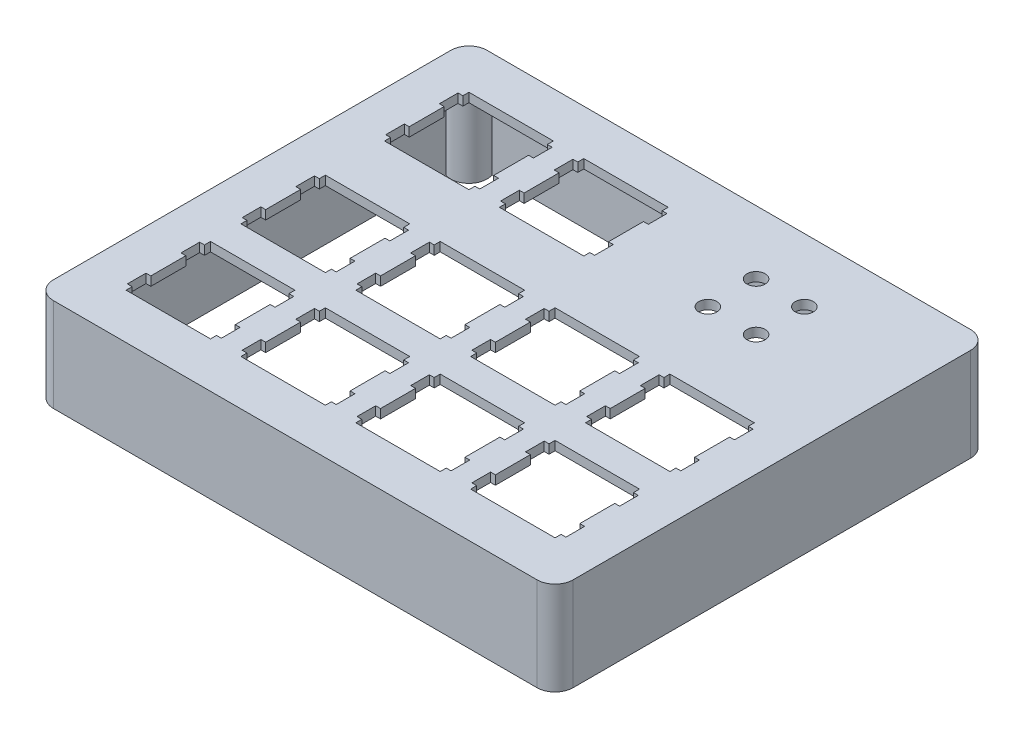
SolidWorks part; units mm, degrees
material "ABS"
ref_plane "Front" through (0, 0, 0) normal (0, 0, 1) x (1, 0, 0)
ref_plane "Top" through (0, 0, 0) normal (0, 1, 0) x (1, 0, 0)
ref_plane "Right" through (0, 0, 0) normal (1, 0, 0) x (0, 0, -1)
sketch "Model" plane through (0, 0, -8.6083) normal (0, 1, 0) x (1, 0, 0)
  line L0 (59.625, 24.9677) -> (64.675, 24.9677) construction
  line L1 (62.15, 24.9677) -> (62.15, 48.7802) construction
  line L3 (58.15, 52.7802) -> (66.15, 52.7802) construction
  line L4 (58.15, 52.7802) -> (58.15, 44.7802) construction
  line L5 (58.15, 44.7802) -> (66.15, 44.7802) construction
  line L6 (66.15, 52.7802) -> (66.15, 44.7802) construction
  line L7 (58.15, 52.7802) -> (66.15, 44.7802) construction
  line L8 (58.15, 44.7802) -> (66.15, 52.7802) construction
  circle A0 centre (58.15, 52.7802) radius 1.5
  circle A1 centre (66.15, 52.7802) radius 1.5
  circle A2 centre (66.15, 44.7802) radius 1.5
  circle A3 centre (58.15, 44.7802) radius 1.5
  point P5 (40.575, 48.7802)
  line B0 (86.201, -8.6083) -> (0, -8.6083)
  line B1 (0, -8.6083) -> (0, 63.3047)
  line B2 (0, 63.3047) -> (86.201, 63.3047)
  line B3 (86.201, 63.3047) -> (86.201, -8.6083)
  line B4 (64.675, 12.9177) -> (64.675, 11.9177)
  line B5 (64.675, 11.9177) -> (63.875, 11.9177)
  line B6 (63.875, 11.9177) -> (63.875, 8.8177)
  line B7 (63.875, 8.8177) -> (64.675, 8.8177)
  line B8 (64.675, 8.8177) -> (64.675, 3.0177)
  line B9 (64.675, 3.0177) -> (63.875, 3.0177)
  line B10 (63.875, 3.0177) -> (63.875, -0.0823)
  line B11 (63.875, -0.0823) -> (64.675, -0.0823)
  line B12 (64.675, -0.0823) -> (64.675, -1.0823)
  line B13 (64.675, -1.0823) -> (78.675, -1.0823)
  line B14 (78.675, -1.0823) -> (78.675, -0.0823)
  line B15 (78.675, -0.0823) -> (79.475, -0.0823)
  line B16 (79.475, -0.0823) -> (79.475, 3.0177)
  line B17 (79.475, 3.0177) -> (78.675, 3.0177)
  line B18 (78.675, 3.0177) -> (78.675, 8.8177)
  line B19 (78.675, 8.8177) -> (79.475, 8.8177)
  line B20 (79.475, 8.8177) -> (79.475, 11.9177)
  line B21 (79.475, 11.9177) -> (78.675, 11.9177)
  line B22 (78.675, 11.9177) -> (78.675, 12.9177)
  line B23 (78.675, 12.9177) -> (64.675, 12.9177)
  line B24 (45.625, 12.9177) -> (45.625, 11.9177)
  line B25 (45.625, 11.9177) -> (44.825, 11.9177)
  line B26 (44.825, 11.9177) -> (44.825, 8.8177)
  line B27 (44.825, 8.8177) -> (45.625, 8.8177)
  line B28 (45.625, 8.8177) -> (45.625, 3.0177)
  line B29 (45.625, 3.0177) -> (44.825, 3.0177)
  line B30 (44.825, 3.0177) -> (44.825, -0.0823)
  line B31 (44.825, -0.0823) -> (45.625, -0.0823)
  line B32 (45.625, -0.0823) -> (45.625, -1.0823)
  line B33 (45.625, -1.0823) -> (59.625, -1.0823)
  line B34 (59.625, -1.0823) -> (59.625, -0.0823)
  line B35 (59.625, -0.0823) -> (60.425, -0.0823)
  line B36 (60.425, -0.0823) -> (60.425, 3.0177)
  line B37 (60.425, 3.0177) -> (59.625, 3.0177)
  line B38 (59.625, 3.0177) -> (59.625, 8.8177)
  line B39 (59.625, 8.8177) -> (60.425, 8.8177)
  line B40 (60.425, 8.8177) -> (60.425, 11.9177)
  line B41 (60.425, 11.9177) -> (59.625, 11.9177)
  line B42 (59.625, 11.9177) -> (59.625, 12.9177)
  line B43 (59.625, 12.9177) -> (45.625, 12.9177)
  line B44 (26.575, 12.9177) -> (26.575, 11.9177)
  line B45 (26.575, 11.9177) -> (25.775, 11.9177)
  line B46 (25.775, 11.9177) -> (25.775, 8.8177)
  line B47 (25.775, 8.8177) -> (26.575, 8.8177)
  line B48 (26.575, 8.8177) -> (26.575, 3.0177)
  line B49 (26.575, 3.0177) -> (25.775, 3.0177)
  line B50 (25.775, 3.0177) -> (25.775, -0.0823)
  line B51 (25.775, -0.0823) -> (26.575, -0.0823)
  line B52 (26.575, -0.0823) -> (26.575, -1.0823)
  line B53 (26.575, -1.0823) -> (40.575, -1.0823)
  line B54 (40.575, -1.0823) -> (40.575, -0.0823)
  line B55 (40.575, -0.0823) -> (41.375, -0.0823)
  line B56 (41.375, -0.0823) -> (41.375, 3.0177)
  line B57 (41.375, 3.0177) -> (40.575, 3.0177)
  line B58 (40.575, 3.0177) -> (40.575, 8.8177)
  line B59 (40.575, 8.8177) -> (41.375, 8.8177)
  line B60 (41.375, 8.8177) -> (41.375, 11.9177)
  line B61 (41.375, 11.9177) -> (40.575, 11.9177)
  line B62 (40.575, 11.9177) -> (40.575, 12.9177)
  line B63 (40.575, 12.9177) -> (26.575, 12.9177)
  line B64 (7.524, 12.9177) -> (7.524, 11.9177)
  line B65 (7.524, 11.9177) -> (6.724, 11.9177)
  line B66 (6.724, 11.9177) -> (6.724, 8.8177)
  line B67 (6.724, 8.8177) -> (7.524, 8.8177)
  line B68 (7.524, 8.8177) -> (7.524, 3.0177)
  line B69 (7.524, 3.0177) -> (6.724, 3.0177)
  line B70 (6.724, 3.0177) -> (6.724, -0.0823)
  line B71 (6.724, -0.0823) -> (7.524, -0.0823)
  line B72 (7.524, -0.0823) -> (7.524, -1.0823)
  line B73 (7.524, -1.0823) -> (21.525, -1.0823)
  line B74 (21.525, -1.0823) -> (21.525, -0.0823)
  line B75 (21.525, -0.0823) -> (22.325, -0.0823)
  line B76 (22.325, -0.0823) -> (22.325, 3.0177)
  line B77 (22.325, 3.0177) -> (21.525, 3.0177)
  line B78 (21.525, 3.0177) -> (21.525, 8.8177)
  line B79 (21.525, 8.8177) -> (22.325, 8.8177)
  line B80 (22.325, 8.8177) -> (22.325, 11.9177)
  line B81 (22.325, 11.9177) -> (21.525, 11.9177)
  line B82 (21.525, 11.9177) -> (21.525, 12.9177)
  line B83 (21.525, 12.9177) -> (7.524, 12.9177)
  line B84 (64.675, 31.9677) -> (64.675, 30.9677)
  line B85 (64.675, 30.9677) -> (63.875, 30.9677)
  line B86 (63.875, 30.9677) -> (63.875, 27.8677)
  line B87 (63.875, 27.8677) -> (64.675, 27.8677)
  line B88 (64.675, 27.8677) -> (64.675, 22.0677)
  line B89 (64.675, 22.0677) -> (63.875, 22.0677)
  line B90 (63.875, 22.0677) -> (63.875, 18.9677)
  line B91 (63.875, 18.9677) -> (64.675, 18.9677)
  line B92 (64.675, 18.9677) -> (64.675, 17.9677)
  line B93 (64.675, 17.9677) -> (78.675, 17.9677)
  line B94 (78.675, 17.9677) -> (78.675, 18.9677)
  line B95 (78.675, 18.9677) -> (79.475, 18.9677)
  line B96 (79.475, 18.9677) -> (79.475, 22.0677)
  line B97 (79.475, 22.0677) -> (78.675, 22.0677)
  line B98 (78.675, 22.0677) -> (78.675, 27.8677)
  line B99 (78.675, 27.8677) -> (79.475, 27.8677)
  line B100 (79.475, 27.8677) -> (79.475, 30.9677)
  line B101 (79.475, 30.9677) -> (78.675, 30.9677)
  line B102 (78.675, 30.9677) -> (78.675, 31.9677)
  line B103 (78.675, 31.9677) -> (64.675, 31.9677)
  line B104 (45.625, 31.9677) -> (45.625, 30.9677)
  line B105 (45.625, 30.9677) -> (44.825, 30.9677)
  line B106 (44.825, 30.9677) -> (44.825, 27.8677)
  line B107 (44.825, 27.8677) -> (45.625, 27.8677)
  line B108 (45.625, 27.8677) -> (45.625, 22.0677)
  line B109 (45.625, 22.0677) -> (44.825, 22.0677)
  line B110 (44.825, 22.0677) -> (44.825, 18.9677)
  line B111 (44.825, 18.9677) -> (45.625, 18.9677)
  line B112 (45.625, 18.9677) -> (45.625, 17.9677)
  line B113 (45.625, 17.9677) -> (59.625, 17.9677)
  line B114 (59.625, 17.9677) -> (59.625, 18.9677)
  line B115 (59.625, 18.9677) -> (60.425, 18.9677)
  line B116 (60.425, 18.9677) -> (60.425, 22.0677)
  line B117 (60.425, 22.0677) -> (59.625, 22.0677)
  line B118 (59.625, 22.0677) -> (59.625, 27.8677)
  line B119 (59.625, 27.8677) -> (60.425, 27.8677)
  line B120 (60.425, 27.8677) -> (60.425, 30.9677)
  line B121 (60.425, 30.9677) -> (59.625, 30.9677)
  line B122 (59.625, 30.9677) -> (59.625, 31.9677)
  line B123 (59.625, 31.9677) -> (45.625, 31.9677)
  line B124 (26.575, 31.9677) -> (26.575, 30.9677)
  line B125 (26.575, 30.9677) -> (25.775, 30.9677)
  line B126 (25.775, 30.9677) -> (25.775, 27.8677)
  line B127 (25.775, 27.8677) -> (26.575, 27.8677)
  line B128 (26.575, 27.8677) -> (26.575, 22.0677)
  line B129 (26.575, 22.0677) -> (25.775, 22.0677)
  line B130 (25.775, 22.0677) -> (25.775, 18.9677)
  line B131 (25.775, 18.9677) -> (26.575, 18.9677)
  line B132 (26.575, 18.9677) -> (26.575, 17.9677)
  line B133 (26.575, 17.9677) -> (40.575, 17.9677)
  line B134 (40.575, 17.9677) -> (40.575, 18.9677)
  line B135 (40.575, 18.9677) -> (41.375, 18.9677)
  line B136 (41.375, 18.9677) -> (41.375, 22.0677)
  line B137 (41.375, 22.0677) -> (40.575, 22.0677)
  line B138 (40.575, 22.0677) -> (40.575, 27.8677)
  line B139 (40.575, 27.8677) -> (41.375, 27.8677)
  line B140 (41.375, 27.8677) -> (41.375, 30.9677)
  line B141 (41.375, 30.9677) -> (40.575, 30.9677)
  line B142 (40.575, 30.9677) -> (40.575, 31.9677)
  line B143 (40.575, 31.9677) -> (26.575, 31.9677)
  line B144 (7.524, 31.9677) -> (7.524, 30.9677)
  line B145 (7.524, 30.9677) -> (6.724, 30.9677)
  line B146 (6.724, 30.9677) -> (6.724, 27.8677)
  line B147 (6.724, 27.8677) -> (7.524, 27.8677)
  line B148 (7.524, 27.8677) -> (7.524, 22.0677)
  line B149 (7.524, 22.0677) -> (6.724, 22.0677)
  line B150 (6.724, 22.0677) -> (6.724, 18.9677)
  line B151 (6.724, 18.9677) -> (7.524, 18.9677)
  line B152 (7.524, 18.9677) -> (7.524, 17.9677)
  line B153 (7.524, 17.9677) -> (21.525, 17.9677)
  line B154 (21.525, 17.9677) -> (21.525, 18.9677)
  line B155 (21.525, 18.9677) -> (22.325, 18.9677)
  line B156 (22.325, 18.9677) -> (22.325, 22.0677)
  line B157 (22.325, 22.0677) -> (21.525, 22.0677)
  line B158 (21.525, 22.0677) -> (21.525, 27.8677)
  line B159 (21.525, 27.8677) -> (22.325, 27.8677)
  line B160 (22.325, 27.8677) -> (22.325, 30.9677)
  line B161 (22.325, 30.9677) -> (21.525, 30.9677)
  line B162 (21.525, 30.9677) -> (21.525, 31.9677)
  line B163 (21.525, 31.9677) -> (7.524, 31.9677)
  line B164 (26.575, 55.7807) -> (26.575, 54.7807)
  line B165 (26.575, 54.7807) -> (25.775, 54.7807)
  line B166 (25.775, 54.7807) -> (25.775, 51.6797)
  line B167 (25.775, 51.6797) -> (26.575, 51.6797)
  line B168 (26.575, 51.6797) -> (26.575, 45.8807)
  line B169 (26.575, 45.8807) -> (25.775, 45.8807)
  line B170 (25.775, 45.8807) -> (25.775, 42.7797)
  line B171 (25.775, 42.7797) -> (26.575, 42.7797)
  line B172 (26.575, 42.7797) -> (26.575, 41.7797)
  line B173 (26.575, 41.7797) -> (40.575, 41.7797)
  line B174 (40.575, 41.7797) -> (40.575, 42.7797)
  line B175 (40.575, 42.7797) -> (41.375, 42.7797)
  line B176 (41.375, 42.7797) -> (41.375, 45.8807)
  line B177 (41.375, 45.8807) -> (40.575, 45.8807)
  line B178 (40.575, 45.8807) -> (40.575, 51.6797)
  line B179 (40.575, 51.6797) -> (41.375, 51.6797)
  line B180 (41.375, 51.6797) -> (41.375, 54.7807)
  line B181 (41.375, 54.7807) -> (40.575, 54.7807)
  line B182 (40.575, 54.7807) -> (40.575, 55.7807)
  line B183 (40.575, 55.7807) -> (26.575, 55.7807)
  line B184 (7.524, 55.7807) -> (7.524, 54.7807)
  line B185 (7.524, 54.7807) -> (6.724, 54.7807)
  line B186 (6.724, 54.7807) -> (6.724, 51.6797)
  line B187 (6.724, 51.6797) -> (7.524, 51.6797)
  line B188 (7.524, 51.6797) -> (7.524, 45.8807)
  line B189 (7.524, 45.8807) -> (6.724, 45.8807)
  line B190 (6.724, 45.8807) -> (6.724, 42.7797)
  line B191 (6.724, 42.7797) -> (7.524, 42.7797)
  line B192 (7.524, 42.7797) -> (7.524, 41.7797)
  line B193 (7.524, 41.7797) -> (21.525, 41.7797)
  line B194 (21.525, 41.7797) -> (21.525, 42.7797)
  line B195 (21.525, 42.7797) -> (22.325, 42.7797)
  line B196 (22.325, 42.7797) -> (22.325, 45.8807)
  line B197 (22.325, 45.8807) -> (21.525, 45.8807)
  line B198 (21.525, 45.8807) -> (21.525, 51.6797)
  line B199 (21.525, 51.6797) -> (22.325, 51.6797)
  line B200 (22.325, 51.6797) -> (22.325, 54.7807)
  line B201 (22.325, 54.7807) -> (21.525, 54.7807)
  line B202 (21.525, 54.7807) -> (21.525, 55.7807)
  line B203 (21.525, 55.7807) -> (7.524, 55.7807)
  dimension "D1" = 3
  dimension "D2" = 8
sketch_block_instance "Block1-1"
sketch_block "Block1"
extrude "Boss-Extrude1" add sketch "Model" against normal blind 1.5
sketch "Sketch1" plane through (0, -1.5, 0) normal (0, -1, 0) x (-1, 0, 0)
  line L1 (0, 0) -> (-86.201, 0)
  line L2 (0, 0) -> (0, 71.913)
  line L3 (0, 71.913) -> (-86.201, 71.913)
  line L4 (-86.201, 0) -> (-86.201, 71.913)
extrude "Extrude-Thin1" add sketch "Sketch1" along normal blind 14 thin thin type one direction reverse wall 2
fillet "Fillet1" radius 3 4 edges at (0, -7.75, 0) (86.201, -7.75, -71.913) (0, -7.75, -71.913) (86.201, -7.75, 0)
sketch "Sketch2" plane through (0, -15.5, 0) normal (0, -1, 0) x (1, 0, 0)
  circle A0 centre (3, -3) radius 3
  arc A1 (3, 0) -> (0, -3) centre (3, -3) ccw construction
  circle A2 centre (83.201, -3) radius 3
  circle A3 centre (3, -68.913) radius 3
  circle A4 centre (83.201, -68.913) radius 3
  arc A5 (83.201, -71.913) -> (86.201, -68.913) centre (83.201, -68.913) ccw construction
  arc A6 (0, -68.913) -> (3, -71.913) centre (3, -68.913) ccw construction
  arc A7 (86.201, -3) -> (83.201, 0) centre (83.201, -3) ccw construction
extrude "Boss-Extrude2" add sketch "Sketch2" against normal up to surface (14 mm away) up to face at (43.1005, -1.5, -35.9565)
hole_wizard "Tap Drill for #2 Helicoil1" positions "Sketch3" profile "Sketch5" hole size "#2-56" standard "ANSI Inch"
sketch "Sketch3" plane through (0, -15.5, 0) normal (0, -1, 0) x (-1, 0, 0)
  point P0 (-3, 3)
  point P3 (-83.201, 3)
  point P6 (-83.201, 68.913)
  point P9 (-3, 68.913)
sketch "Sketch5" plane through (3, -15.5, -3) normal (1, 0, 0) x (0, 0, -1)
  line L0 (0, 0) -> (0, 7.0658)
  line L1 (0, 7.0658) -> (1.1913, 6.35)
  line L2 (1.1913, 6.35) -> (1.1913, 0)
  line L5 (1.1913, 0) -> (0, 0)
  line L10 (0, 7.0658) -> (-1.1913, 6.35) construction
  line L11 (0, -6.35) -> (0, 107.95) construction
  dimension "Hole Dia." = 2.3825
  dimension "Hole Depth" = 6.35
  dimension "Drill Angle" = 118
sketch "Sketch6" plane through (0, 0, -71.913) normal (0, 0, -1) x (-1, 0, 0)
  line L0 (-3, -15.5) -> (-83.201, -15.5) construction
  line L2 (-47.1005, -22) -> (-39.1005, -22)
  line L3 (-47.1005, -22) -> (-47.1005, -9)
  line L4 (-47.1005, -9) -> (-39.1005, -9)
  line L5 (-39.1005, -22) -> (-39.1005, -9)
  line L6 (-47.1005, -22) -> (-39.1005, -9) construction
  line L7 (-47.1005, -9) -> (-39.1005, -22) construction
  point P0 (-43.1005, -15.5)
  point P1 (-43.1005, -15.5)
  dimension "D1" = 6.5
  dimension "D2" = 8
extrude "Cut-Extrude1" cut sketch "Sketch6" against normal up to surface (2 mm away) up to face at (43.1005, -8.5, -69.913)
